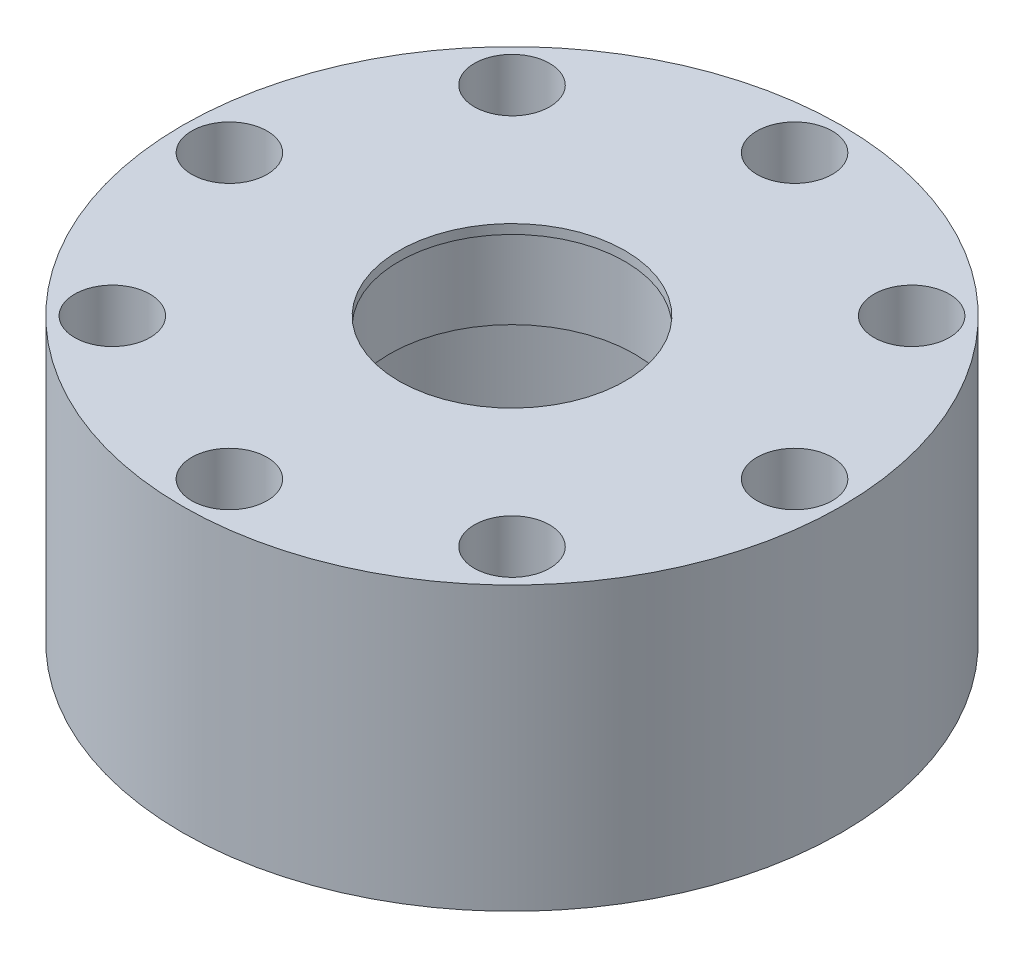
SolidWorks part; units mm, degrees
ref_plane "Front Plane" through (0, 0, 0) normal (0, 0, 1) x (1, 0, 0)
ref_plane "Top Plane" through (0, 0, 0) normal (0, 1, 0) x (1, 0, 0)
ref_plane "Right Plane" through (0, 0, 0) normal (1, 0, 0) x (0, 0, -1)
sketch "Sketch1" plane through (0, 0, 0) normal (0, 0, 1) x (1, 0, 0)
  line L0 (12.5, 0) -> (17.5, 0)
  line L1 (17.5, 0) -> (17.5, 15)
  line L4 (6.5, 10) -> (7.5, 10)
  line L5 (12.5, 10) -> (12.5, 0)
  line L6 (0, 0) -> (0, 14.6637) construction
  line L7 (10, 10) -> (10, 12)
  line L8 (10, 12) -> (7.5, 12)
  line L9 (7.5, 12) -> (7.5, 10)
  line L10 (10, 10) -> (12.5, 10)
  line L13 (6, 15) -> (17.5, 15)
  line L14 (6.5, 10) -> (6.5, 14.5)
  line L15 (6.5, 14.5) -> (6, 14.5)
  line L16 (6, 14.5) -> (6, 15)
  dimension "D1" = 35
  dimension "D2" = 25
  dimension "D3" = 0.5
  dimension "D4" = 10
  dimension "D5" = 20
  dimension "D6" = 15
  dimension "D7" = 2
  dimension "D8" = 5
  dimension "D9" = 0.5
  dimension "D10" = 1
revolve "Revolve1" add sketch "Sketch1" angle 360 about L6
sketch "Sketch2" plane through (0, 15, 0) normal (0, 1, 0) x (1, 0, 0)
  line L0 (0, 0) -> (15, 0) construction
  line L1 (0, 0) -> (10.6066, -10.6066) construction
  circle A0 centre (15, 0) radius 2
  circle A1 centre (0, 0) radius 15 construction
  circle A2 centre (10.6066, -10.6066) radius 2
  circle A3 centre (0, -15) radius 2
  circle A4 centre (-10.6066, -10.6066) radius 2
  circle A5 centre (-15, 0) radius 2
  circle A6 centre (-10.6066, 10.6066) radius 2
  circle A7 centre (0, 15) radius 2
  circle A8 centre (10.6066, 10.6066) radius 2
  dimension "D1" = 4
  dimension "D2" = 30
  dimension "D4" = 45
  dimension "D3" = 8
extrude "Cut-Extrude1" cut sketch "Sketch2" against normal through all
